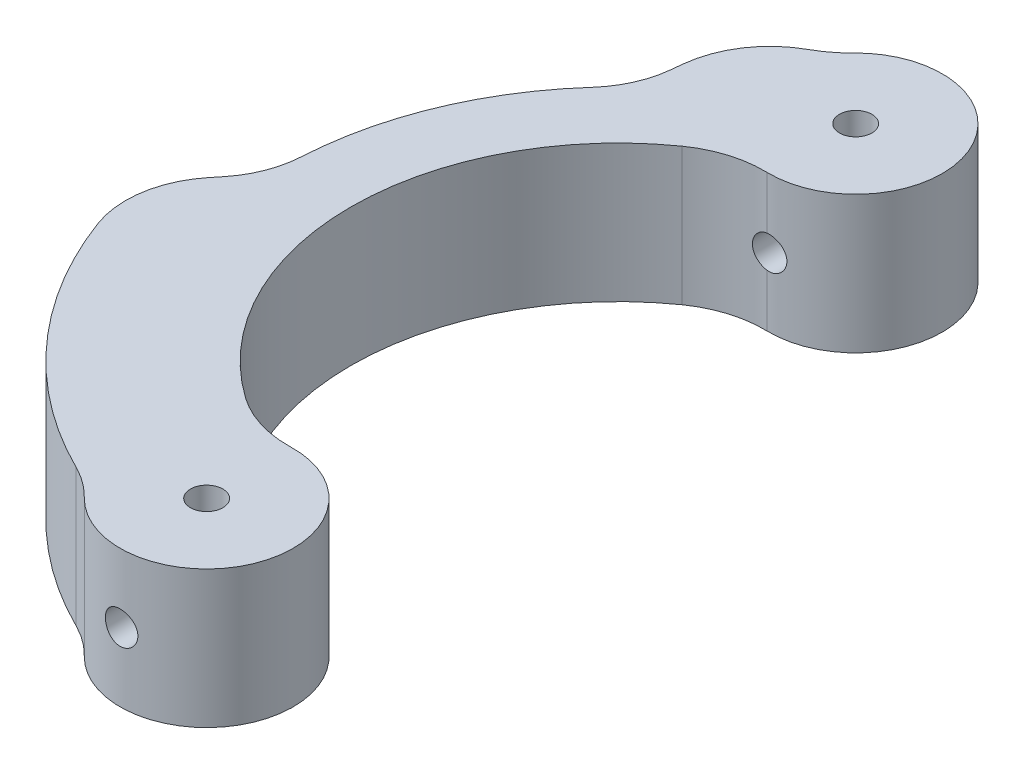
SolidWorks part; units mm, degrees
material "Delrin 2700 NC010, Low Viscosity Acetal Copolymer (SS)"
ref_plane "Front Plane" through (0, 0, 0) normal (0, 0, 1) x (1, 0, 0)
ref_plane "Top Plane" through (0, 0, 0) normal (0, 1, 0) x (1, 0, 0)
ref_plane "Right Plane" through (0, 0, 0) normal (1, 0, 0) x (0, 0, -1)
sketch "Sketch1" plane through (0, 0, 0) normal (0, 1, 0) x (1, 0, 0)
  line L0 (0, 0) -> (3.1975, -11.9332) construction
  line L1 (3.1975, -11.9332) -> (0, -23.8664) construction
  arc A0 (0, 0) -> (0, -23.8664) centre (3.1975, -11.9332) ccw
  arc A1 (-1.6435, 6.1336) -> (-1.6435, -30) centre (3.1975, -11.9332) ccw
  arc A2 (-1.6435, 6.1336) -> (0, 0) centre (-0.8218, 3.0668) cw
  arc A3 (0, -23.8664) -> (-1.6435, -30) centre (-0.8218, -26.9332) cw
  circle A4 centre (-0.8218, 3.0668) radius 0.75
  circle A5 centre (-0.8218, -26.9332) radius 0.75
  dimension "D1" = 6.35
  dimension "D2" = 1.5
  dimension "D3" = 150
  dimension "D4" = 30
extrude "Boss-Extrude1" add sketch "Sketch1" along normal blind 6.35
sketch "Sketch2" plane through (0, 6.35, 0) normal (0, 1, 0) x (1, 0, 0)
  circle A0 centre (-0.8218, 3.0668) radius 1.5
  circle A1 centre (-0.8218, 3.0668) radius 4
  circle A2 centre (-0.8218, -26.9332) radius 1.5
  circle A3 centre (-0.8218, -26.9332) radius 4
  dimension "D1" = 8
extrude "Boss-Extrude2" add sketch "Sketch2" against normal up to surface (6.35 mm away) up to face at (-0.8218, 0, -2.3168)
fillet "Fillet1" radius 5 4 edges at (-4.1667, 3.175, 29.1266) (-2.0387, 3.175, 23.1228) (-2.0387, 3.175, 0.7436) (-4.1667, 3.175, -5.2602)
sketch "Sketch4" plane through (0, 6.35, 0) normal (0, 1, 0) x (1, 0, 0)
  line L0 (-10.0283, 1.2926) -> (-7.7833, -0.9524)
  line L1 (-15.5067, -11.9332) -> (-12.3317, -11.9332)
  line L2 (-12.3317, -11.9332) -> (3.1975, -11.9332) construction
  line L3 (-7.7833, -0.9524) -> (3.1975, -11.9332) construction
  line L4 (-0.8218, 3.0668) -> (3.1975, -11.9332) construction
  arc A0 (-5.0779, 4.8407) -> (-5.0779, -28.7071) centre (3.1975, -11.9332) ccw construction
  arc A1 (-7.7833, -0.9524) -> (-12.3317, -11.9332) centre (3.1975, -11.9332) ccw
  arc A3 (-3.9393, -1.849) -> (-3.9393, -22.0174) centre (3.1975, -11.9332) ccw construction
  arc M7 (-5.0779, 4.8407) -> (-5.0779, -28.7071) centre (3.1975, -11.9332) ccw
  dimension "D3" = 3.175
  dimension "D1" = 45
  dimension "D2" = 30
extrude "Cut-Extrude1" cut sketch "Sketch4" against normal through all and the other way through all contours A1 L0 L1 M7 region at (-12.2571, 6.35, 5.5317)
chamfer "Chamfer1" distance 3.25 angle 45 2 edges at (-15.5067, 3.175, 11.9332) (-10.0283, 3.175, -1.2926)
fillet "Fillet2" radius 4.5 4 edges at (-7.4165, 3.175, 0.5975) (-12.3233, 3.175, 12.4435) (-6.9512, 3.175, -3.7783) (-15.0884, 3.175, 15.8667)
sketch "Sketch5" plane through (0, 0, 0) normal (0, 0, 1) x (1, 0, 0)
  line L1 (3.1782, 6.35) -> (-0.8218, 3.175) construction
  line L2 (-0.8218, 3.175) -> (3.1782, 0) construction
  line L3 (-1.5718, 0) -> (-0.8218, 3.175) construction
  line L4 (-0.8218, 3.175) -> (-0.0718, 0) construction
  line L5 (-3.6965, 0) -> (3.1782, 0) construction
  line L6 (-1.5718, 6.35) -> (-1.5718, 0) construction
  circle A0 centre (-0.8218, 3.175) radius 0.75
  point P7 (-1.6815, 0)
  point P13 (-1.4924, 0)
  dimension "D1" = 1.5
extrude "Cut-Extrude2" cut sketch "Sketch5" against normal through all and the other way through all
